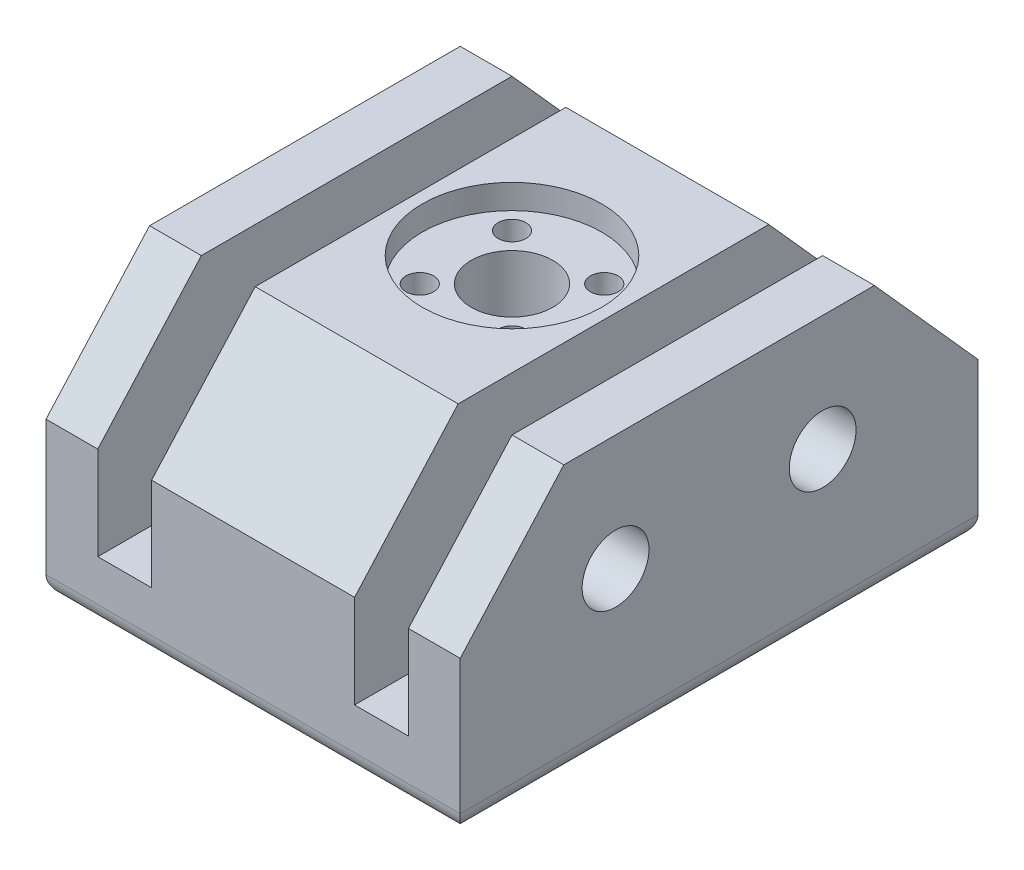
SolidWorks part; units mm, degrees
ref_plane "Front Plane" through (0, 0, 0) normal (0, 0, 1) x (1, 0, 0)
ref_plane "Top Plane" through (0, 0, 0) normal (0, 1, 0) x (1, 0, 0)
ref_plane "Right Plane" through (0, 0, 0) normal (1, 0, 0) x (0, 0, -1)
sketch "Sketch1" plane through (0, 0, 0) normal (1, 0, 0) x (0, 0, -1)
  line L1 (0, 0) -> (63.5, 0)
  line L2 (0, 0) -> (0, 6.35)
  line L3 (0, 6.35) -> (63.5, 6.35)
  line L4 (63.5, 0) -> (63.5, 6.35)
  dimension "D1" = 6.35
  dimension "D2" = 63.5
extrude "Boss-Extrude1" add sketch "Sketch1" against normal blind 50.8
sketch "Sketch2" plane through (0, 0, 0) normal (1, 0, 0) x (0, 0, -1)
  line L0 (0, 6.35) -> (0, 19.05)
  line L1 (0, 19.05) -> (12.7, 33.249)
  line L2 (12.7, 33.249) -> (50.8, 33.249)
  line L3 (50.8, 33.249) -> (63.5, 19.05)
  line L4 (63.5, 19.05) -> (63.5, 6.35)
  line L5 (63.5, 6.35) -> (0, 6.35)
  point P7 (31.75, 33.249)
  point P10 (31.75, 6.35)
  dimension "D1" = 38.1
  dimension "D2" = 12.7
  dimension "D3" = 12.7
  dimension "D4" = 19.05
  dimension "D5" = 19.05
extrude "Boss-Extrude2" add sketch "Sketch2" against normal blind 50.8
sketch "Sketch10" plane through (0, 0, -63.5) normal (0, 0, -1) x (-1, 0, 0)
  line L1 (50.8, 33.249) -> (0, 33.249) construction
  line L3 (6.35, 7.62) -> (6.35, 33.249)
  line L4 (6.35, 33.249) -> (12.954, 33.249)
  line L5 (12.954, 7.62) -> (12.954, 33.249)
  line L6 (6.35, 7.62) -> (12.954, 7.62)
  line L8 (50.8, 0) -> (0, 0) construction
  point P11 (12.954, 7.62)
  dimension "D1" = 7.62
  dimension "D2" = 6.604
  dimension "D3" = 6.35
extrude "Cut-Extrude1" cut sketch "Sketch10" against normal through all
pattern_linear "LPattern3" count 2 spacing 31.496 along (-1, 0, 0) of "Cut-Extrude1"
sketch "Sketch11" plane through (0, 0, 0) normal (1, 0, 0) x (0, 0, -1)
  circle A0 centre (19.05, 19.05) radius 4.0957
  circle A1 centre (19.05, 19.05) radius 7.9375 construction
  circle A2 centre (44.45, 19.05) radius 4.0958
  circle A3 centre (44.45, 19.05) radius 7.9375 construction
  dimension "D1" = 8.1915
  dimension "D3" = 15.875
  dimension "D4" = 8.1915
  dimension "D6" = 15.875
  dimension "D2" = 6.35
  dimension "D5" = 6.35
extrude "Cut-Extrude2" cut sketch "Sketch11" against normal through all
sketch "Sketch14" plane through (0, 33.249, 0) normal (0, 1, 0) x (1, 0, 0)
  line L3 (-37.846, 12.7) -> (-37.846, 50.8) construction
  point P0 (-25.4, 31.75)
  point P4 (-37.846, 31.75)
  dimension "D1" = 12.446
sketch "Sketch17" plane through (0, 40.0201, -44.7438) normal (0, 0.6667, -0.7454) x (-1, 0, 0)
  line L0 (12.954, -28.1343) -> (12.954, -9.0843) construction
  line L1 (37.846, -9.0843) -> (12.954, -9.0843) construction
  point P0 (25.4, -18.6093)
  point P4 (12.954, -18.6093)
  point P7 (25.4, -9.0843)
sketch "Sketch18" plane through (0, 8.4667, 9.466) normal (0, 0.6667, 0.7454) x (1, 0, 0)
  line L0 (-12.954, 33.249) -> (-12.954, 14.199) construction
  line L1 (-37.846, 33.249) -> (-12.954, 33.249) construction
  point P0 (-25.4, 23.724)
  point P1 (-25.4, 23.724)
  point P4 (-12.954, 23.724)
  point P7 (-25.4, 33.249)
ref_plane "Plane2" through (0, 33.02, 0) normal (0, -1, 0) x (-1, 0, 0)
fillet "Fillet1" radius 2.54 4 edges at (0, 0, -31.75) (-50.8, 0, -31.75) (-25.4, 0, 0) (-25.4, 0, -63.5)
sketch "Sketch21" plane through (0, 0, 0) normal (0, -1, 0) x (1, 0, 0)
  line L0 (-25.4, -63.5) -> (-25.4, 0) construction
  line L1 (-50.8, -63.5) -> (0, -63.5) construction
  line L2 (-50.8, 0) -> (0, 0) construction
  line L3 (-50.8, -31.75) -> (0, -31.75) construction
  line L4 (-50.8, 0) -> (-50.8, -63.5) construction
  line L5 (0, 0) -> (0, -63.5) construction
  circle A0 centre (-31.0569, -37.4069) radius 1.7
  circle A1 centre (-31.0569, -26.0931) radius 1.7
  circle A2 centre (-19.7431, -26.0931) radius 1.7
  circle A3 centre (-19.7431, -37.4069) radius 1.7
  point P14 (-25.4, -31.75)
  point P24 (-25.4, -31.75)
  dimension "D1" = 3.4
  dimension "D2" = 8
  dimension "D4" = 4
sketch "Sketch22" plane through (0, 33.249, 0) normal (0, -1, 0) x (1, 0, 0)
  line L1 (-25.4, -63.5) -> (-25.4, 0) construction
  line L2 (-50.8, -63.5) -> (0, -63.5) construction
  line L3 (-50.8, 0) -> (0, 0) construction
  line L4 (0, -31.75) -> (-50.8, -31.75) construction
  line L6 (0, 0) -> (0, -63.5) construction
  line L7 (-50.8, 0) -> (-50.8, -63.5) construction
  circle A1 centre (-25.4, -31.75) radius 11
  dimension "D1" = 22
extrude "Cut-Extrude7" cut sketch "Sketch21" against normal up to next
extrude "Cut-Extrude8" cut sketch "Sketch22" along normal blind 3
sketch "Sketch24" plane through (0, 0, 0) normal (0, -1, 0) x (1, 0, 0)
  line L0 (-25.4, -63.5) -> (-25.4, 0) construction
  line L1 (-50.8, -63.5) -> (0, -63.5) construction
  line L2 (-50.8, 0) -> (0, 0) construction
  line L3 (0, -31.75) -> (-50.8, -31.75) construction
  line L4 (0, 0) -> (0, -63.5) construction
  line L5 (-50.8, 0) -> (-50.8, -63.5) construction
  circle A0 centre (-25.4, -31.75) radius 5
  dimension "D1" = 10
extrude "Cut-Extrude10" cut sketch "Sketch24" against normal through all
